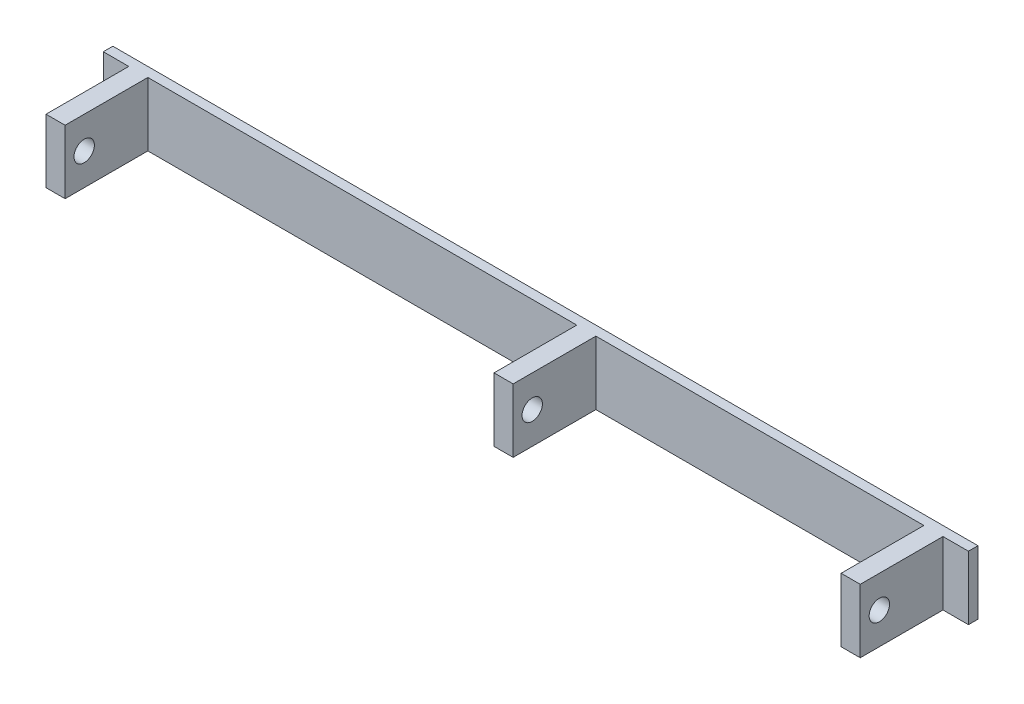
SolidWorks part; units mm, degrees
ref_plane "前视基准面" through (0, 0, 0) normal (0, 0, 1) x (1, 0, 0)
ref_plane "上视基准面" through (0, 0, 0) normal (0, 1, 0) x (1, 0, 0)
ref_plane "右视基准面" through (0, 0, 0) normal (1, 0, 0) x (0, 0, -1)
sketch "草图1" plane through (0, 0, 0) normal (0, 0, 1) x (1, 0, 0)
  line L1 (-67.95, -5) -> (67.95, -5)
  line L2 (-67.95, -5) -> (-67.95, 5)
  line L3 (-67.95, 5) -> (67.95, 5)
  line L4 (67.95, -5) -> (67.95, 5)
  line L5 (-67.95, -5) -> (67.95, 5) construction
  line L6 (-67.95, 5) -> (67.95, -5) construction
  point P0 (0, 0)
  dimension "D1" = 10
  dimension "D2" = 135.9
extrude "凸台-拉伸1" add sketch "草图1" along normal blind 1.5
sketch "草图2" plane through (0, 0, 1.5) normal (0, 0, 1) x (1, 0, 0)
  line L0 (67.95, 5) -> (-67.95, 5) construction
  line L1 (-63.95, 5) -> (-60.95, 5)
  line L2 (-63.95, 5) -> (-63.95, -5)
  line L3 (-63.95, -5) -> (-60.95, -5)
  line L4 (-60.95, 5) -> (-60.95, -5)
  line L5 (-67.95, -5) -> (67.95, -5) construction
  line L6 (67.95, -5) -> (67.95, 5) construction
  line L7 (60.95, 5) -> (63.95, 5)
  line L8 (60.95, 5) -> (60.95, -5)
  line L9 (60.95, -5) -> (63.95, -5)
  line L10 (63.95, 5) -> (63.95, -5)
  line L11 (-67.95, 5) -> (-67.95, -5) construction
  line L12 (6.3282, -3.75) -> (6.3282, 3.75) construction
  line L13 (6.4282, 5) -> (9.4282, 5)
  line L14 (6.4282, 5) -> (6.4282, -5)
  line L15 (6.4282, -5) -> (9.4282, -5)
  line L16 (9.4282, 5) -> (9.4282, -5)
  dimension "D1" = 3
  dimension "D2" = 4
  dimension "D3" = 3
  dimension "D4" = 4
  dimension "D5" = 3
  dimension "D6" = 0.1
extrude "凸台-拉伸2" add sketch "草图2" along normal blind 13
sketch "草图3" plane through (63.95, 0, 0) normal (1, 0, 0) x (0, 0, -1)
  line L2 (-14.5, 0) -> (-9.2904, 0) construction
  line L3 (-14.5, -5) -> (-14.5, 5) construction
  line L4 (0, -5) -> (0, 5) construction
  circle A0 centre (-11.5, 0) radius 1.6
  dimension "D1" = 3.2
  dimension "D2" = 11.5
extrude "切除-拉伸1" cut sketch "草图3" against normal up to surface (127.9 mm away) up to face at (-63.95, 0, 8)
